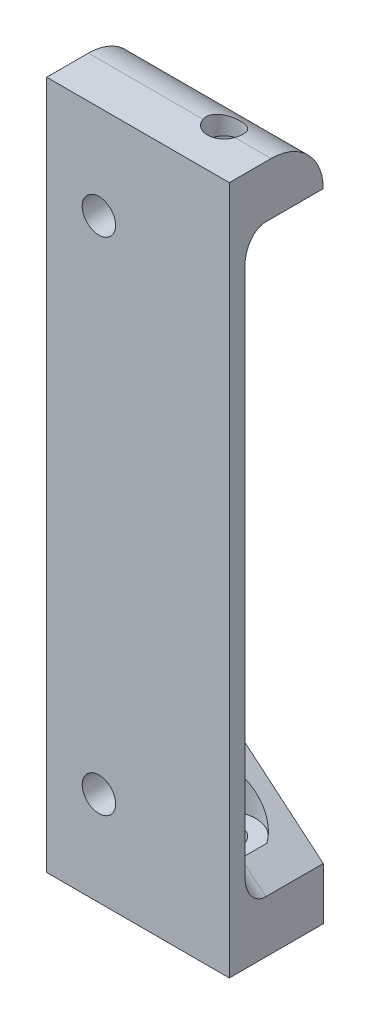
SolidWorks part; units mm, degrees
material "ABS"
ref_plane "Front" through (0, 0, 0) normal (0, 0, 1) x (1, 0, 0)
ref_plane "Top" through (0, 0, 0) normal (0, 1, 0) x (1, 0, 0)
ref_plane "Right" through (0, 0, 0) normal (1, 0, 0) x (0, 0, -1)
sketch "Esquisse1" plane through (0, 0, 0) normal (0, 0, 1) x (1, 0, 0)
  line L1 (0, -33) -> (17.5, -33)
  line L2 (0, -33) -> (0, 33)
  line L3 (0, 33) -> (17.5, 33)
  line L4 (17.5, -33) -> (17.5, 33)
  dimension "D1" = 17.5
  dimension "D2" = 66
extrude "Boss.-Extru.1" add sketch "Esquisse1" along normal blind 9
sketch "Esquisse3" plane through (0, 0, 9) normal (0, 0, 1) x (1, 0, 0)
  line L0 (50, 0) -> (-50, 0) construction
  line L1 (0, 33) -> (0, -33) construction
  circle A0 centre (5, 24) radius 1.6
  circle A1 centre (5, -24) radius 1.6
  dimension "D2" = 3.2
  dimension "D1" = 48
  dimension "D3" = 5
extrude "Enlèv. mat.-Extru.2" cut sketch "Esquisse3" against normal through all
sketch "Esquisse4" plane through (0, 0, 9) normal (0, 0, 1) x (1, 0, 0)
  line L1 (6.5877, 26.75) -> (3.4123, 26.75)
  line L2 (3.4123, 26.75) -> (1.8246, 24)
  line L3 (1.8246, 24) -> (3.4123, 21.25)
  line L4 (3.4123, 21.25) -> (6.5877, 21.25)
  line L5 (6.5877, 21.25) -> (8.1754, 24)
  line L6 (8.1754, 24) -> (6.5877, 26.75)
  line L7 (8.1754, -24) -> (6.5877, -21.25)
  line L8 (6.5877, -21.25) -> (3.4123, -21.25)
  line L9 (3.4123, -21.25) -> (1.8246, -24)
  line L10 (1.8246, -24) -> (3.4123, -26.75)
  line L11 (3.4123, -26.75) -> (6.5877, -26.75)
  line L12 (6.5877, -26.75) -> (8.1754, -24)
  circle A0 centre (5, 24) radius 2.75 construction
  circle A1 centre (5, -24) radius 2.75 construction
  dimension "D1" = 5.5
extrude "Enlèv. mat.-Extru.3" cut sketch "Esquisse4" against normal through all from offset 3 offset against normal yes
sketch "Esquisse5" plane through (0, 33, 0) normal (0, 1, 0) x (1, 0, 0)
  line L0 (17.5, -9) -> (0, -9) construction
  line L1 (0, -9) -> (0, 0) construction
  line L2 (17.5, -9) -> (17.5, 0) construction
  circle A0 centre (12.5, -4.5) radius 1.6
  dimension "D3" = 3.2
  dimension "D1" = 4.5
  dimension "D2" = 12.5
  dimension "D4" = 5
extrude "Enlèv. mat.-Extru.4" cut sketch "Esquisse5" against normal through all
sketch "Esquisse6" plane through (0, 0, 0) normal (0, 0, -1) x (-1, 0, 0)
  line L0 (-17.5, -33) -> (-17.5, 33) construction
  line L1 (-17.5, 28) -> (-2, 14.994)
  line L2 (-17.5, 28) -> (-17.5, -28)
  line L3 (-17.5, -28) -> (-2, -14.994)
  line L4 (-2, 14.994) -> (-2, -14.994)
  line L5 (0, 33) -> (0, -33) construction
  point P4 (-17.5, 0)
  point P7 (-2, 0)
  dimension "D1" = 5
  dimension "D2" = 2
  dimension "D3" = 50
extrude "Enlèv. mat.-Extru.5" cut sketch "Esquisse6" against normal offset from surface (7.5 mm away) 1.5 up to face at (6.6, 24, 9)
sketch "Esquisse7" plane through (0, -33, 0) normal (0, -1, 0) x (1, 0, 0)
  line L1 (15.25, 6.0877) -> (12.5, 7.6754)
  line L2 (12.5, 7.6754) -> (9.75, 6.0877)
  line L3 (9.75, 6.0877) -> (9.75, 2.9123)
  line L4 (9.75, 2.9123) -> (12.5, 1.3246)
  line L5 (12.5, 1.3246) -> (15.25, 2.9123)
  line L6 (15.25, 2.9123) -> (15.25, 6.0877)
  circle A0 centre (12.5, 4.5) radius 2.75 construction
  circle A1 centre (12.5, 4.5) radius 1.6 construction
  dimension "D1" = 5.5
extrude "Enlèv. mat.-Extru.6" cut sketch "Esquisse7" against normal blind 3
fillet "Congé2" radius 2 5 edges at (9.75, 21.497, 7.5) (2, 14.994, 3.75) (2, 0, 7.5) (2, -14.994, 3.75) (9.75, -21.497, 7.5)
sketch "Esquisse8" plane through (0, -30, 0) normal (0, -1, 0) x (1, 0, 0)
  circle A0 centre (12.5, 4.5) radius 3
  circle A1 centre (12.5, 4.5) radius 1.6 construction
  dimension "D1" = 6
extrude "Enlèv. mat.-Extru.7" cut sketch "Esquisse8" against normal blind 10 from offset 4 offset against normal yes
sketch "Esquisse9" plane through (0, 33, 0) normal (0, 1, 0) x (1, 0, 0)
  line L1 (15.25, -2.9123) -> (12.5, -1.3246)
  line L2 (12.5, -1.3246) -> (9.75, -2.9123)
  line L3 (9.75, -2.9123) -> (9.75, -6.0877)
  line L4 (9.75, -6.0877) -> (12.5, -7.6754)
  line L5 (12.5, -7.6754) -> (15.25, -6.0877)
  line L6 (15.25, -6.0877) -> (15.25, -2.9123)
  circle A0 centre (12.5, -4.5) radius 2.75 construction
  circle A1 centre (12.5, -4.5) radius 1.6 construction
  dimension "D1" = 5.5
extrude "Enlèv. mat.-Extru.8" cut sketch "Esquisse9" against normal blind 10 from offset 2 offset against normal yes
fillet "Congé3" radius 5 1 edges at (8.75, 33, 0)
equation "\"D2@Esquisse5\"=7.5+\"D3@Esquisse3\""
